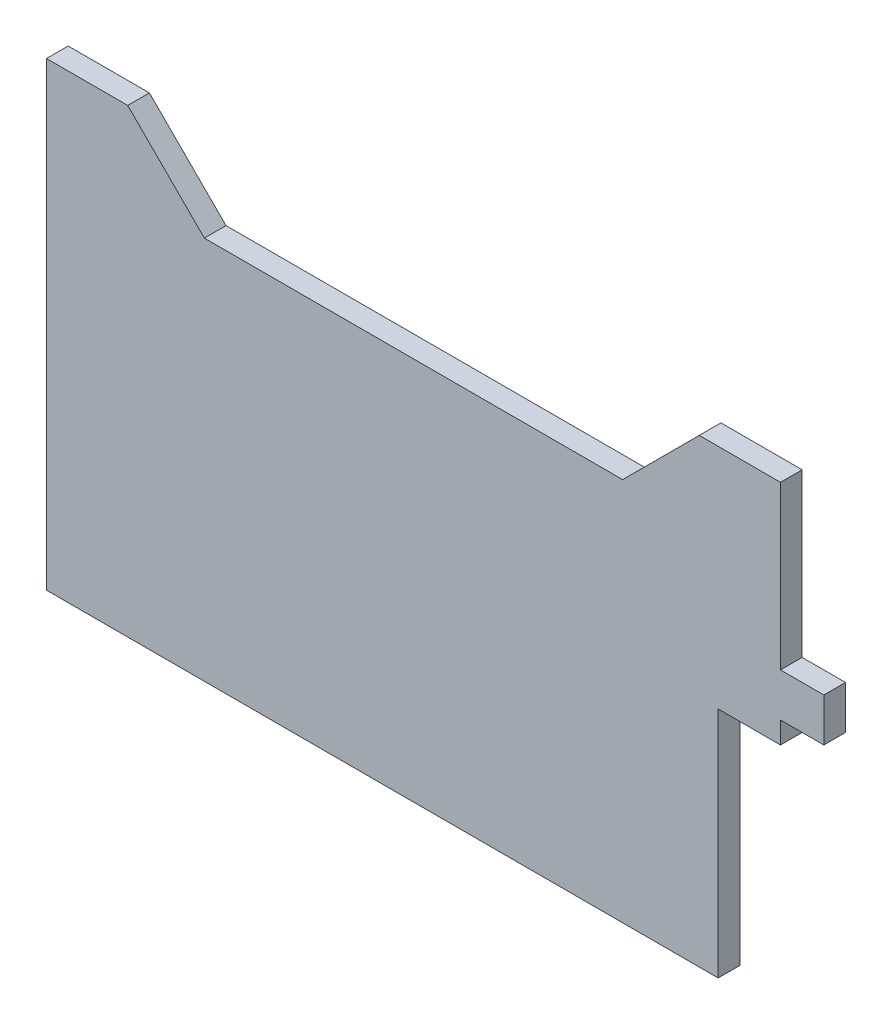
SolidWorks part; units mm, degrees
ref_plane "Front Plane" through (0, 0, 0) normal (0, 0, 1) x (1, 0, 0)
ref_plane "Top Plane" through (0, 0, 0) normal (0, 1, 0) x (1, 0, 0)
ref_plane "Right Plane" through (0, 0, 0) normal (1, 0, 0) x (0, 0, -1)
sketch "Sketch1" plane through (0, 0, 0) normal (0, 0, 1) x (1, 0, 0)
  line L0 (40.3337, 32.2009) -> (47.8337, 32.2009)
  line L1 (-87.6663, -27.7991) -> (40.3337, -27.7991) construction
  line L2 (-87.6663, -27.7991) -> (-87.6663, 32.2009)
  line L3 (-87.6663, 32.2009) -> (40.3337, 32.2009)
  line L4 (40.3337, -27.7991) -> (40.3337, 32.2009) construction
  line L6 (47.8337, 15.2009) -> (40.3337, 15.2009)
  line L11 (47.8337, 32.2009) -> (47.8337, 15.2009) construction
  line L12 (47.8337, 32.2009) -> (47.8337, 27.2009)
  line L14 (47.8337, 27.2009) -> (55.8337, 27.2009)
  line L15 (55.8337, 27.2009) -> (55.8337, 19.2009)
  line L16 (55.8337, 19.2009) -> (47.8337, 19.2009)
  line L17 (47.8337, 19.2009) -> (47.8337, 15.2009)
  line L18 (36.3337, -27.7991) -> (36.3337, 15.2009)
  line L19 (36.3337, 15.2009) -> (40.3337, 15.2009)
  line L20 (-87.6663, -27.7991) -> (36.3337, -27.7991)
  point P12 (0, 0)
  dimension "D3" = 5
  dimension "D4" = 7.5
  dimension "D5" = 8
  dimension "D1" = 128
  dimension "D6" = 8
  dimension "D2" = 60
  dimension "D7" = 4
  dimension "D8" = 4
extrude "Boss-Extrude1" add sketch "Sketch1" along normal blind 4
sketch "Sketch2" plane through (0, 0, 0) normal (0, 0, 1) x (1, 0, 0)
  line L0 (-87.6663, 32.2009) -> (47.8337, 32.2009)
  line L1 (47.8337, 32.2009) -> (47.8337, 57.2009)
  line L2 (47.8337, 57.2009) -> (32.8337, 57.2009)
  line L3 (32.8337, 57.2009) -> (18.6916, 43.0588)
  line L4 (18.6916, 43.0588) -> (-58.5241, 43.0588)
  line L5 (-58.5241, 43.0588) -> (-72.6663, 57.2009)
  line L6 (-72.6663, 57.2009) -> (-87.6663, 57.2009)
  line L7 (-87.6663, 57.2009) -> (-87.6663, 32.2009)
  dimension "D1" = 25
  dimension "D2" = 20
  dimension "D3" = 15
  dimension "D4" = 135
extrude "Boss-Extrude2" add sketch "Sketch2" along normal blind 4
